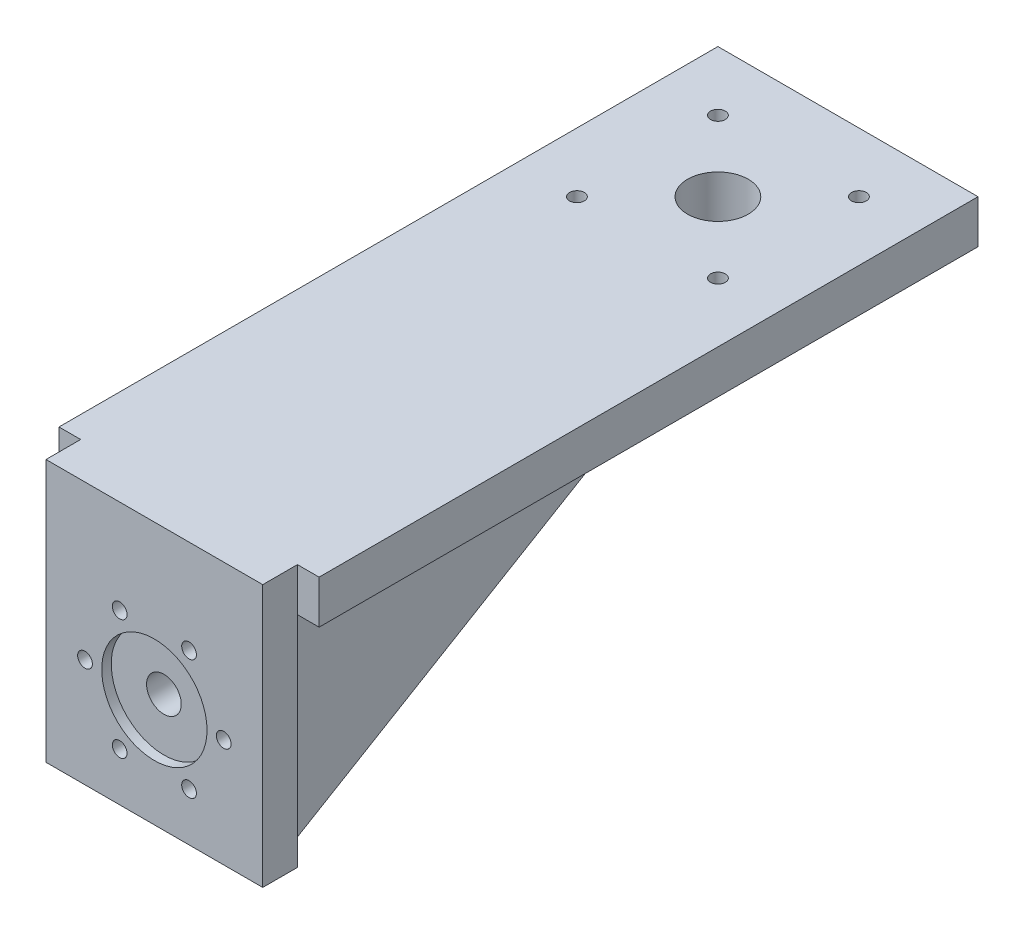
SolidWorks part; units mm, degrees
material "6061-T6 (SS)"
ref_plane "Front Plane" through (0, 0, 0) normal (0, 0, 1) x (1, 0, 0)
ref_plane "Top Plane" through (0, 0, 0) normal (0, 1, 0) x (1, 0, 0)
ref_plane "Right Plane" through (0, 0, 0) normal (1, 0, 0) x (0, 0, -1)
ref_plane "PL_Yaw_Plate_base" through (0, 0, -8) normal (0, 0, 1) x (1, 0, 0)
sketch "SK_Yaw_Plate" plane through (0, 0, -8) normal (0, 0, 1) x (1, 0, 0)
  line L0 (-25, 35.5) -> (25, 35.5)
  line L1 (25, 35.5) -> (25, -25)
  line L2 (25, -25) -> (-25, -25)
  line L3 (-25, -25) -> (-25, 35.5)
  circle A0 centre (16, 0) radius 1.7
  circle A1 centre (8, -13.8564) radius 1.7
  circle A2 centre (-8, -13.8564) radius 1.7
  circle A3 centre (-16, 0) radius 1.7
  circle A4 centre (-8, 13.8564) radius 1.7
  circle A5 centre (8, 13.8564) radius 1.7
  circle A6 centre (0, 0) radius 4
  dimension "D9_SK_Yaw_Plate" = 3.4
  dimension "D11_SK_Yaw_Plate" = 3.4
  dimension "D14_SK_Yaw_Plate" = 3.4
  dimension "D17_SK_Yaw_Plate" = 3.4
  dimension "D19_SK_Yaw_Plate" = 3.4
  dimension "D22_SK_Yaw_Plate" = 3.4
  dimension "D25_SK_Yaw_Plate" = 8
  dimension "P1" = 25
  dimension "P2" = 35.5
  dimension "P3" = 25
  dimension "P4" = 35.5
  dimension "P5" = 25
  dimension "P6" = 25
  dimension "P7" = 25
  dimension "P8" = 25
  dimension "P10" = 16
  dimension "P12" = 8
  dimension "P13" = 13.8564
  dimension "P15" = 8
  dimension "P16" = 13.8564
  dimension "P18" = 16
  dimension "P20" = 8
  dimension "P21" = 13.8564
  dimension "P23" = 8
  dimension "P24" = 13.8564
extrude "Yaw_Plate" add sketch "SK_Yaw_Plate" along normal blind 8
sketch "SK_Yaw_Pilot_Recess" plane through (0, 0, 0) normal (0, 0, 1) x (1, 0, 0)
  circle A0 centre (0, 0) radius 12.15
  dimension "D1_SK_Yaw_Pilot_Recess" = 24.3
extrude "Yaw_Pilot_Recess" cut sketch "SK_Yaw_Pilot_Recess" against normal blind 2.2
ref_plane "PL_Elbow_Plate_base" through (0, 25.5, 0) normal (0, 1, 0) x (1, 0, 0)
sketch "SK_Elbow_Plate" plane through (0, 25.5, 0) normal (0, 1, 0) x (1, 0, 0)
  line L0 (-30, 8) -> (30, 8)
  line L1 (30, 8) -> (30, 160)
  line L2 (30, 160) -> (-30, 160)
  line L3 (-30, 160) -> (-30, 8)
  circle A0 centre (16.2635, 146.2635) radius 1.7
  circle A1 centre (-16.2635, 146.2635) radius 1.7
  circle A2 centre (-16.2635, 113.7365) radius 1.7
  circle A3 centre (16.2635, 113.7365) radius 1.7
  circle A4 centre (0, 130) radius 7
  dimension "D9_SK_Elbow_Plate" = 3.4
  dimension "D12_SK_Elbow_Plate" = 3.4
  dimension "D15_SK_Elbow_Plate" = 3.4
  dimension "D18_SK_Elbow_Plate" = 3.4
  dimension "D21_SK_Elbow_Plate" = 14
  dimension "P1" = 30
  dimension "P2" = 8
  dimension "P3" = 30
  dimension "P4" = 8
  dimension "P5" = 30
  dimension "P6" = 160
  dimension "P7" = 30
  dimension "P8" = 160
  dimension "P10" = 16.2635
  dimension "P11" = 146.2635
  dimension "P13" = 16.2635
  dimension "P14" = 146.2635
  dimension "P16" = 16.2635
  dimension "P17" = 113.7365
  dimension "P19" = 16.2635
  dimension "P20" = 113.7365
  dimension "P22" = 130
extrude "Elbow_Plate" add sketch "SK_Elbow_Plate" along normal blind 10
ref_plane "PL_Gusset_Front_base" through (18.5, 0, 0) normal (1, 0, 0) x (0, 0, -1)
sketch "SK_Gusset_Front" plane through (18.5, 0, 0) normal (1, 0, 0) x (0, 0, -1)
  line L0 (7.5, 26) -> (7.5, -20)
  line L1 (7.5, -20) -> (85, 26)
  line L2 (85, 26) -> (7.5, 26)
  dimension "P1" = 7.5
  dimension "P2" = 26
  dimension "P3" = 7.5
  dimension "P4" = 20
  dimension "P5" = 85
  dimension "P6" = 26
extrude "Gusset_Front" add sketch "SK_Gusset_Front" along normal blind 6
ref_plane "PL_Gusset_Back_base" through (-24.5, 0, 0) normal (1, 0, 0) x (0, 0, -1)
sketch "SK_Gusset_Back" plane through (-24.5, 0, 0) normal (1, 0, 0) x (0, 0, -1)
  line L0 (7.5, 26) -> (7.5, -20)
  line L1 (7.5, -20) -> (85, 26)
  line L2 (85, 26) -> (7.5, 26)
  dimension "P1" = 7.5
  dimension "P2" = 26
  dimension "P3" = 7.5
  dimension "P4" = 20
  dimension "P5" = 85
  dimension "P6" = 26
extrude "Gusset_Back" add sketch "SK_Gusset_Back" along normal blind 6
equation "\"Elbow_z\"= -130"
equation "\"Elbow_plate_t\"= 10"
equation "\"Yaw_plate_t\"= 8"
